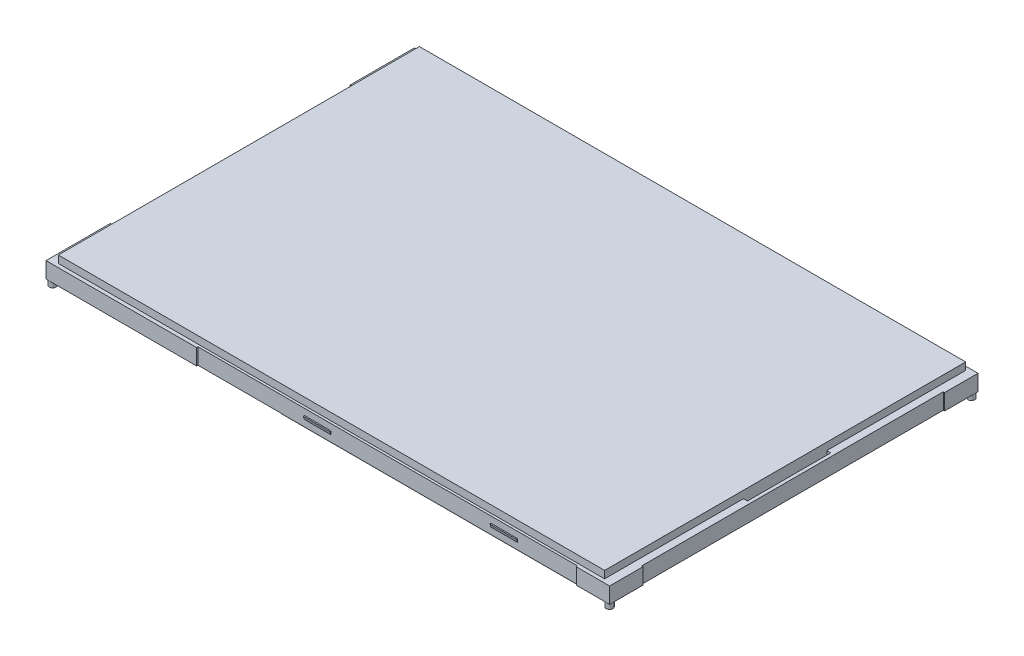
SolidWorks part; units mm, degrees
material "ABS"
ref_plane "Front" through (0, 0, 0) normal (0, 0, 1) x (1, 0, 0)
ref_plane "Top" through (0, 0, 0) normal (0, 1, 0) x (1, 0, 0)
ref_plane "Right" through (0, 0, 0) normal (1, 0, 0) x (0, 0, -1)
sketch "Sketch1" plane through (0, 0, 0) normal (0, 1, 0) x (1, 0, 0)
  line L1 (-42.3, -27.65) -> (42.3, -27.65)
  line L2 (-42.3, -27.65) -> (-42.3, 27.65)
  line L3 (-42.3, 27.65) -> (42.3, 27.65)
  line L4 (42.3, -27.65) -> (42.3, 27.65)
  line L5 (-42.3, -27.65) -> (42.3, 27.65) construction
  line L6 (-42.3, 27.65) -> (42.3, -27.65) construction
  point P0 (0, 0)
  dimension "D1" = 84.6
  dimension "D2" = 55.3
extrude "Boss-Extrude1" add sketch "Sketch1" against normal blind 2.4
sketch "Sketch2" plane through (0, 0, 0) normal (0, 1, 0) x (1, 0, 0)
  line L1 (-41, -27.1) -> (41, -27.1)
  line L2 (-41, -27.1) -> (-41, 27.1)
  line L3 (-41, 27.1) -> (41, 27.1)
  line L4 (41, -27.1) -> (41, 27.1)
  line L5 (-41, -27.1) -> (41, 27.1) construction
  line L6 (-41, 27.1) -> (41, -27.1) construction
  point P0 (0, 0)
  dimension "D1" = 82
  dimension "D2" = 54.2
extrude "Boss-Extrude2" add sketch "Sketch2" along normal blind 1.1
sketch "Sketch3" plane through (0, -2.4, 0) normal (0, -1, 0) x (1, 0, 0)
  line L0 (-42.3, 27.65) -> (42.3, 27.65) construction
  line L1 (-42.3, -27.65) -> (-42.3, 27.65) construction
  line L2 (42.3, -27.65) -> (-42.3, -27.65) construction
  line L3 (42.3, 27.65) -> (42.3, -27.65) construction
  circle A0 centre (-41.8, 27.15) radius 0.5
  circle A1 centre (41.8, 27.15) radius 0.5
  circle A2 centre (41.8, -27.15) radius 0.5
  circle A3 centre (-41.8, -27.15) radius 0.5
  dimension "D1" = 0.5
  dimension "D2" = 0.5
  dimension "D3" = 0.5
  dimension "D4" = 0.5
  dimension "D6" = 0.5
  dimension "D7" = 0.5
  dimension "D8" = 0.5
  dimension "D9" = 1
  dimension "D10" = 1
  dimension "D11" = 1
  dimension "D12" = 1
  dimension "D5" = 0.5
extrude "Boss-Extrude3" add sketch "Sketch3" along normal blind 0.8
sketch "Sketch4" plane through (0, -2.4, 0) normal (0, -1, 0) x (1, 0, 0)
  line L0 (0, 0) -> (-59.8368, 0) construction
  line L1 (-42.3, -27.15) -> (-42.3, 27.15) construction
  line L2 (-39.7, -22.4) -> (-41.3, -22.4)
  line L3 (-39.1, -21.8) -> (-39.1, 21.8)
  line L4 (-39.7, 22.4) -> (-41.3, 22.4)
  line L5 (-41.9, -21.8) -> (-41.9, 21.8)
  line L6 (-39.1, -22.4) -> (-41.9, 22.4) construction
  line L7 (-39.1, 22.4) -> (-41.9, -22.4) construction
  arc A0 (-39.7, -22.4) -> (-39.1, -21.8) centre (-39.7, -21.8) ccw
  arc A1 (-41.3, -22.4) -> (-41.9, -21.8) centre (-41.3, -21.8) cw
  arc A2 (-39.1, 21.8) -> (-39.7, 22.4) centre (-39.7, 21.8) ccw
  arc A3 (-41.3, 22.4) -> (-41.9, 21.8) centre (-41.3, 21.8) ccw
  point P3 (-40.5, 0)
  dimension "D4" = 0.6
  dimension "D1" = 2.8
  dimension "D2" = 44.8
  dimension "D3" = 0.4
extrude "Cut-Extrude1" cut sketch "Sketch4" against normal blind 1
sketch "Sketch5" plane through (0, 0, 27.65) normal (0, 0, 1) x (1, 0, 0)
  line L0 (-41, 0) -> (41, 0) construction
  line L1 (-19.7, 0) -> (37.3, 0)
  line L2 (-19.7, 0) -> (-19.7, -2.4)
  line L3 (-19.7, -2.4) -> (37.3, -2.4)
  line L4 (37.3, 0) -> (37.3, -2.4)
  line L5 (-41.8, -2.4) -> (41.8, -2.4) construction
  line L6 (-42.3, -2.4) -> (-42.3, 0) construction
  line L7 (42.3, -2.4) -> (42.3, 0) construction
  point P8 (-42.3, -1.2)
  point P11 (42.3, -1.2)
  dimension "D1" = 22.6
  dimension "D2" = 5
extrude "Cut-Extrude2" cut sketch "Sketch5" against normal blind 0.2
mirror "Mirror1" about plane through (0, 0, 0) normal (0, 0, 1) of "Cut-Extrude2"
sketch "Sketch6" plane through (42.3, 0, 0) normal (1, 0, 0) x (0, 0, -1)
  line L0 (-27.65, 0) -> (27.65, 0) construction
  line L1 (-22.65, 0) -> (22.65, 0)
  line L2 (-22.65, 0) -> (-22.65, -2.4)
  line L3 (-22.65, -2.4) -> (22.65, -2.4)
  line L4 (22.65, 0) -> (22.65, -2.4)
  line L5 (-27.15, -2.4) -> (27.15, -2.4) construction
  line L6 (-27.65, 0) -> (-27.65, -2.4) construction
  line L7 (27.65, -2.4) -> (27.65, 0) construction
  point P8 (-27.65, -1.2)
  point P11 (27.65, -1.2)
  dimension "D1" = 5
  dimension "D2" = 5
extrude "Cut-Extrude3" cut sketch "Sketch6" against normal blind 0.2
sketch "Sketch7" plane through (0, -2.4, 0) normal (0, -1, 0) x (1, 0, 0)
  line L0 (-19.7, 27.45) -> (37.3, 27.45) construction
  line L1 (-7.3, 27.35) -> (37.3, 27.35)
  line L2 (-7.3, 27.35) -> (-7.3, 24.35)
  line L3 (-7.3, 24.35) -> (37.3, 24.35)
  line L4 (37.3, 27.35) -> (37.3, 24.35)
  line L5 (42.3, 27.15) -> (42.3, 22.65) construction
  line L6 (-42.3, -27.15) -> (-42.3, 27.15) construction
  dimension "D1" = 3
  dimension "D2" = 0.1
  dimension "D3" = 5
  dimension "D4" = 35
extrude "Boss-Extrude4" add sketch "Sketch7" along normal blind 0.15
mirror "Mirror2" about plane through (0, 0, 0) normal (0, 0, 1) of "Boss-Extrude4"
sketch "Sketch8" plane through (0, 0, 0) normal (0, 1, 0) x (1, 0, 0)
  line L0 (41, 0) -> (42.1, 0) construction
  line L1 (41, -27.1) -> (41, 27.1) construction
  line L2 (42.1, 22.65) -> (42.1, -22.65) construction
  line L3 (41, -27.1) -> (41, 27.1) construction
  line L4 (41.6, -6.25) -> (41, -6.25)
  line L5 (41.6, -6.25) -> (41.6, 6.25)
  line L6 (41.6, 6.25) -> (41, 6.25)
  line L7 (41, -6.25) -> (41, 6.25)
  line L8 (41.6, -6.25) -> (41, 6.25) construction
  line L9 (41.6, 6.25) -> (41, -6.25) construction
  point P6 (41.3, 0)
  dimension "D1" = 12.5
  dimension "D2" = 0.6
extrude "Cut-Extrude4" cut sketch "Sketch8" against normal blind 1
sketch "Sketch9" plane through (0, 0, 27.45) normal (0, 0, 1) x (1, 0, 0)
  line L0 (-19.7, -1.2) -> (37.3, -1.2) construction
  line L1 (-19.7, 0) -> (-19.7, -2.4) construction
  line L2 (37.3, -2.4) -> (37.3, 0) construction
  line L4 (0.3, -1.45) -> (-3.7, -1.45)
  line L5 (0.3, -1.45) -> (0.3, -0.95)
  line L6 (0.3, -0.95) -> (-3.7, -0.95)
  line L7 (-3.7, -1.45) -> (-3.7, -0.95)
  line L8 (0.3, -1.45) -> (-3.7, -0.95) construction
  line L9 (0.3, -0.95) -> (-3.7, -1.45) construction
  line L10 (28.3, -1.45) -> (24.3, -1.45)
  line L11 (28.3, -1.45) -> (28.3, -0.95)
  line L12 (28.3, -0.95) -> (24.3, -0.95)
  line L13 (24.3, -1.45) -> (24.3, -0.95)
  line L14 (28.3, -1.45) -> (24.3, -0.95) construction
  line L15 (28.3, -0.95) -> (24.3, -1.45) construction
  point P6 (-1.7, -1.2)
  point P11 (26.3, -1.2)
  dimension "D1" = 0.5
  dimension "D2" = 4
  dimension "D3" = 18
  dimension "D4" = 4
  dimension "D5" = 0.5
  dimension "D6" = 11
extrude "Boss-Extrude5" add sketch "Sketch9" along normal blind 0.2
chamfer "Chamfer1" distance 0.2 angle 70 2 edges at (26.3, -1.45, 27.65) (-1.7, -1.45, 27.65) first distance on face at (26.3, -1.45, 27.55) first distance on face at (-1.7, -1.45, 27.55)
mirror "Mirror4" about plane through (0, 0, 0) normal (0, 0, 1) of "Boss-Extrude5", "Chamfer1"
sketch "Sketch10" plane through (-42.3, 0, 0) normal (-1, 0, 0) x (0, 0, 1)
  line L0 (-27.1, 0) -> (27.1, 0) construction
  line L1 (-18, -1.5) -> (18, -1.5)
  line L2 (-18, -1.5) -> (-18, 0)
  line L3 (-18, 0) -> (18, 0)
  line L4 (18, -1.5) -> (18, 0)
  line L5 (-18, -1.5) -> (18, 0) construction
  line L6 (-18, 0) -> (18, -1.5) construction
  line L7 (0, 0) -> (0, -2.4) construction
  line L8 (-27.15, -2.4) -> (27.15, -2.4) construction
  point P0 (0, -0.75)
  dimension "D1" = 1.5
  dimension "D2" = 36
  dimension "D3" = 0
extrude "Cut-Extrude5" cut sketch "Sketch10" against normal blind 10
sketch "Sketch12" plane through (-32.3, 0, 0) normal (-1, 0, 0) x (0, 0, 1)
  line L0 (0, 0) -> (0, -1.5) construction
  line L1 (-18, -1.5) -> (18, -1.5) construction
  line L2 (-18, -0.75) -> (18, -0.75) construction
  line L3 (-18, 0) -> (-18, -1.5) construction
  line L4 (18, -1.5) -> (18, 0) construction
sketch "Sketch13" plane through (0, 0, 0) normal (0, 0, 1) x (1, 0, 0)
  line L0 (-32.3, -0.75) -> (-42.05, -0.75)
  line L1 (-32.3, 0) -> (-32.3, -1.5) construction
  line L2 (-42.05, -2.7) -> (-27.3, -5.4)
  line L3 (-17.3, -8.4) -> (-4.8, -8.4)
  line L5 (-19.7, -2.4) -> (37.3, -2.4) construction
  line L6 (-32.3, -0.65) -> (-42.0589, -0.65)
  line L7 (-42.068, -2.7984) -> (-27.3188, -5.4982)
  line L8 (-17.3024, -8.5) -> (-4.8, -8.5)
  line L9 (-32.3, -0.85) -> (-42.0407, -0.85)
  line L10 (-42.032, -2.6016) -> (-27.2812, -5.3018)
  line L11 (-17.2976, -8.3) -> (-4.8, -8.3)
  line L12 (-32.3, -0.65) -> (-32.3, -0.85)
  line L13 (-4.8, -8.3) -> (-4.8, -8.5)
  line L14 (-27.3, -6.2) -> (-27.3, -7.8) construction
  line L15 (-4.8, -8.8) -> (-4.8, -7.8) construction
  line L16 (-17.3, -6.2) -> (-17.3, -7.8) construction
  line L17 (-41.8, -2.4) -> (-19.7, -2.4) construction
  arc A0 (-42.05, -0.75) -> (-42.05, -2.7) centre (-41.8715, -1.725) ccw
  arc A1 (-42.0589, -0.65) -> (-42.068, -2.7984) centre (-41.8715, -1.725) ccw
  arc A2 (-42.0407, -0.85) -> (-42.032, -2.6016) centre (-41.8715, -1.725) ccw
  spline S0 degree 3 poles (-27.3, -5.4) (-22.8907, -6.2848) (-21.8176, -8.1854) (-17.3, -8.4) knots 0 0 0 0 1 1 1 1
  spline S1 degree 1 poles (-27.3188, -5.4982) (-17.3024, -8.5) knots 0 0 1 1 construction
  spline S2 degree 3 poles (-27.3188, -5.4982) (-27.056, -5.551) (-26.5176, -5.6721) (-25.5723, -5.9325) (-24.5217, -6.3002) (-23.4176, -6.7729) (-22.3818, -7.2481) (-21.3357, -7.694) (-20.2023, -8.0778) (-19.1138, -8.3182) (-18.1337, -8.4461) (-17.5741, -8.4871) (-17.3024, -8.5) knots 0.000063 0.000063 0.000063 0.000063 0.06257 0.125077 0.250091 0.375105 0.500119 0.625133 0.750147 0.875161 0.937668 1.000175 1.000175 1.000175 1.000175
  spline S3 degree 1 poles (-27.2812, -5.3018) (-17.2976, -8.3) knots 0 0 1 1 construction
  spline S4 degree 3 poles (-27.2812, -5.3018) (-27.0153, -5.3551) (-26.4709, -5.4776) (-25.5139, -5.7411) (-24.4503, -6.1132) (-23.3369, -6.5899) (-22.3011, -7.065) (-21.2654, -7.5065) (-20.1512, -7.884) (-19.0823, -8.1204) (-18.1179, -8.2466) (-17.5656, -8.2872) (-17.2976, -8.3) knots -0.000063 -0.000063 -0.000063 -0.000063 0.06243 0.124923 0.249909 0.374895 0.499881 0.624867 0.749852 0.874838 0.937331 0.999824 0.999824 0.999824 0.999824
  dimension "D1" = 7
  dimension "D2" = 9.75
  dimension "D3" = 0.1
  dimension "D4" = 0
  dimension "D5" = 0
  dimension "D6" = 6
  dimension "D7" = 0
  dimension "D8" = 0
  dimension "D9" = 0.1
  dimension "D10" = 3
  dimension "D11" = 0.3
extrude "Boss-Extrude7" add sketch "Sketch13" along normal blind 12.5 and the other way blind 12.5 contours L7 S2 L8 L13 L3 S0 L2 A0 L0 L12 L6 A1 | S4 L10 A2 L9 L12 L0 A0 L2 S0 L3 L13 L11 region at (-32.6882, -0.8, 0) region at (-37.175, -0.711, 0)
